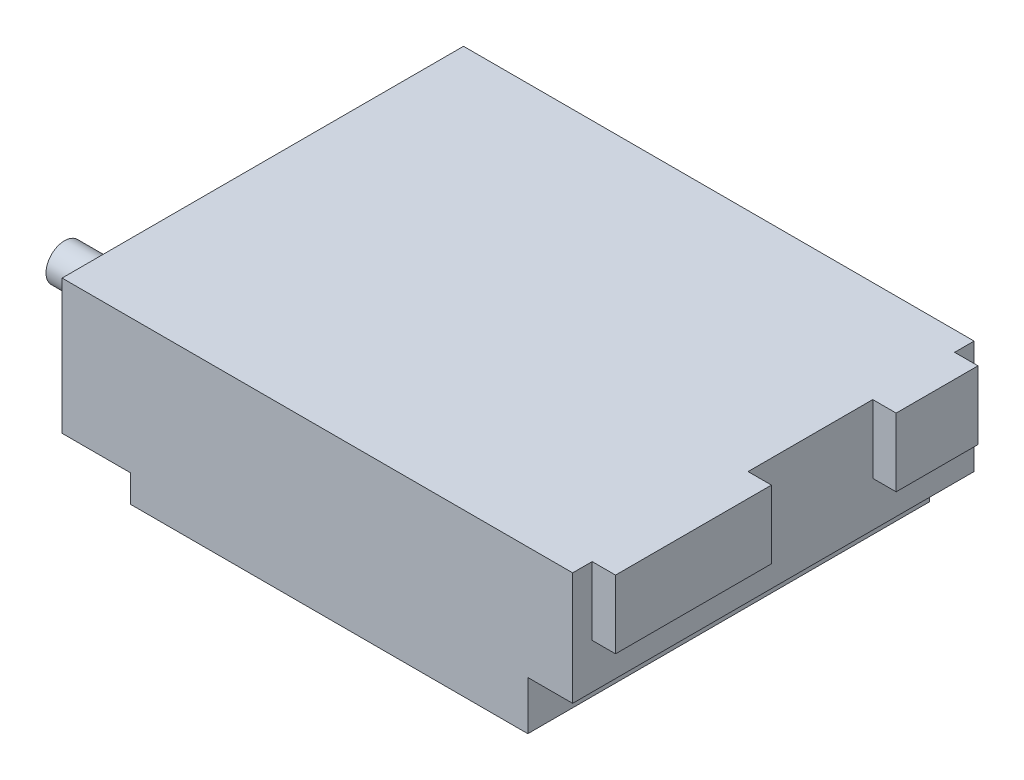
SolidWorks part; units mm, degrees
ref_plane "Front Plane" through (0, 0, 0) normal (0, 0, 1) x (1, 0, 0)
ref_plane "Top Plane" through (0, 0, 0) normal (0, 1, 0) x (1, 0, 0)
ref_plane "Right Plane" through (0, 0, 0) normal (1, 0, 0) x (0, 0, -1)
sketch "Sketch1" plane through (0, 0, 0) normal (0, 1, 0) x (1, 0, 0)
  line L1 (-13.1, 10.3) -> (13.1, 10.3)
  line L2 (-13.1, 10.3) -> (-13.1, -10.3)
  line L3 (-13.1, -10.3) -> (13.1, -10.3)
  line L4 (13.1, 10.3) -> (13.1, -10.3)
  line L5 (-13.1, 10.3) -> (13.1, -10.3) construction
  line L6 (-13.1, -10.3) -> (13.1, 10.3) construction
  point P0 (0, 0)
  dimension "D1" = 26.2
  dimension "D2" = 20.6
extrude "Boss-Extrude1" add sketch "Sketch1" along normal blind 8.3
sketch "Sketch2" plane through (13.1, 0, 0) normal (1, 0, 0) x (0, 0, -1)
  line L0 (-10.3, 8.3) -> (10.3, 8.3) construction
  line L1 (-9.3, 8.3) -> (-1.3, 8.3)
  line L2 (-9.3, 8.3) -> (-9.3, 4.8)
  line L3 (-9.3, 4.8) -> (-1.3, 4.8)
  line L4 (-1.3, 8.3) -> (-1.3, 4.8)
  line L5 (-10.3, 8.3) -> (-10.3, 0) construction
  line L6 (10.3, 8.3) -> (10.3, 0) construction
  line L7 (9.3, 8.3) -> (5.1, 8.3)
  line L8 (9.3, 8.3) -> (9.3, 4.8)
  line L9 (9.3, 4.8) -> (5.1, 4.8)
  line L10 (5.1, 8.3) -> (5.1, 4.8)
  dimension "D1" = 8
  dimension "D2" = 3.5
  dimension "D3" = 1
  dimension "D4" = 4.2
  dimension "D5" = 1
extrude "Boss-Extrude2" add sketch "Sketch2" along normal blind 1.2
sketch "Sketch3" plane through (-13.1, 0, 0) normal (-1, 0, 0) x (0, 0, 1)
  circle A0 centre (5.1748, 3.9453) radius 0.95
  dimension "D1" = 1.9
extrude "Boss-Extrude3" add sketch "Sketch3" along normal blind 5
sketch "Sketch4" plane through (0, 0, 0) normal (0, -1, 0) x (1, 0, 0)
  line L0 (13.1, -10.3) -> (-13.1, -10.3) construction
  line L1 (13.1, 10.3) -> (10.8, 10.3)
  line L2 (13.1, 10.3) -> (13.1, -10.3)
  line L3 (13.1, -10.3) -> (10.8, -10.3)
  line L4 (10.8, 10.3) -> (10.8, -10.3)
  dimension "D1" = 2.3
extrude "Cut-Extrude1" cut sketch "Sketch4" against normal blind 2.5
sketch "Sketch5" plane through (0, 0, 0) normal (0, -1, 0) x (1, 0, 0)
  line L0 (10.8, -10.3) -> (-13.1, -10.3) construction
  line L1 (-13.1, 10.3) -> (-9.6, 10.3)
  line L2 (-13.1, 10.3) -> (-13.1, -10.3)
  line L3 (-13.1, -10.3) -> (-9.6, -10.3)
  line L4 (-9.6, 10.3) -> (-9.6, -10.3)
  dimension "D1" = 3.5
extrude "Cut-Extrude2" cut sketch "Sketch5" against normal blind 1.4
